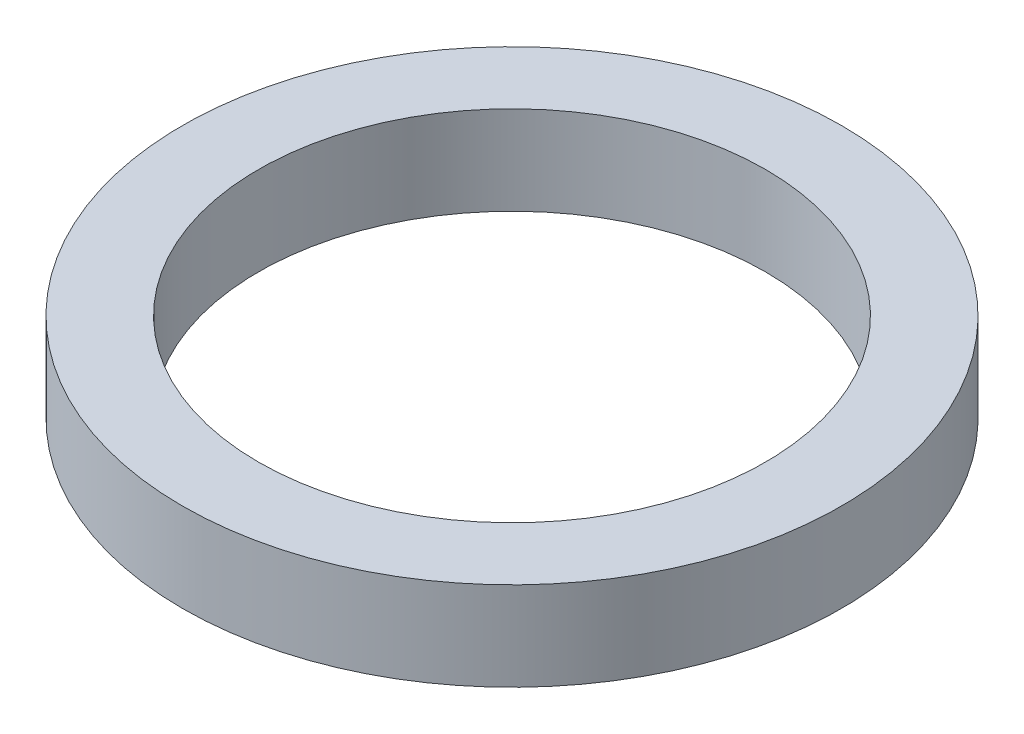
SolidWorks part; units mm, degrees
ref_plane "Front Plane" through (0, 0, 0) normal (0, 0, 1) x (1, 0, 0)
ref_plane "Top Plane" through (0, 0, 0) normal (0, 1, 0) x (1, 0, 0)
ref_plane "Right Plane" through (0, 0, 0) normal (1, 0, 0) x (0, 0, -1)
sketch "Sketch1" plane through (0, 0, 0) normal (0, 1, 0) x (1, 0, 0)
  circle A0 centre (0, 0) radius 2.5
  circle A1 centre (0, 0) radius 5
  dimension "D1" = 10
  dimension "D2" = 5
extrude "Boss-Extrude1" [suppressed] add sketch "Sketch1" along normal blind 4
sketch "Sketch2" [suppressed] plane through (0, 0, 0) normal (0, 1, 0) x (1, 0, 0)
  circle A0 centre (0, 0) radius 7.5
  circle A1 centre (0, 0) radius 14
  dimension "D1" = 15
  dimension "D2" = 28
extrude "Boss-Extrude2" [suppressed] add sketch "Sketch2" along normal blind 8
sketch "Sketch3" [suppressed] plane through (0, 0, 0) normal (0, 1, 0) x (1, 0, 0)
  circle A0 centre (0, 0) radius 25
  circle A1 centre (0, 0) radius 32.5
  dimension "D1" = 65
  dimension "D2" = 50
extrude "Boss-Extrude3" [suppressed] add sketch "Sketch3" along normal blind 7
sketch "Sketch4" plane through (0, 0, 0) normal (0, 1, 0) x (1, 0, 0)
  circle A0 centre (0, 0) radius 5
  circle A1 centre (0, 0) radius 7.5
  dimension "D1" = 10
  dimension "D2" = 15
extrude "Boss-Extrude4" [suppressed] add sketch "Sketch4" along normal blind 4
sketch "Sketch5" plane through (0, 0, 0) normal (0, 1, 0) x (1, 0, 0)
  circle A0 centre (0, 0) radius 20
  circle A1 centre (0, 0) radius 26
  dimension "D1" = 40
  dimension "D2" = 52
extrude "Boss-Extrude5" add sketch "Sketch5" along normal blind 7
